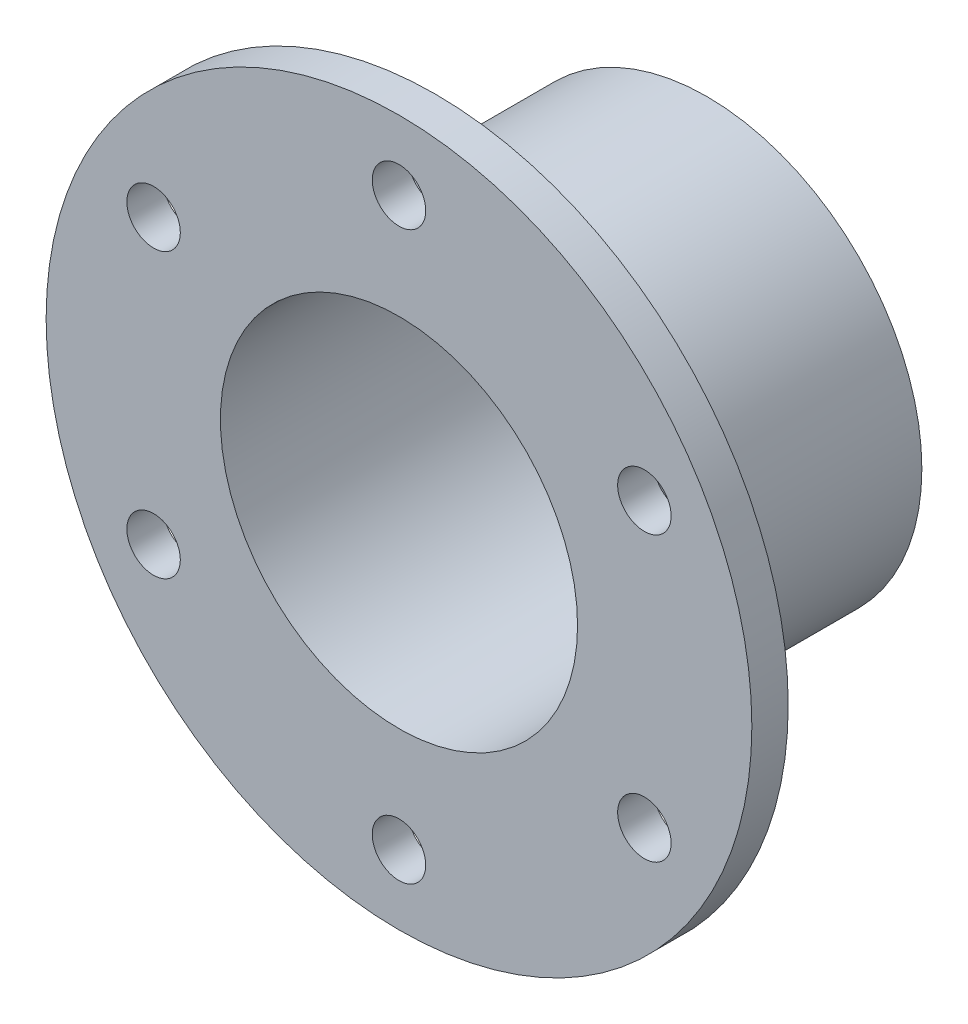
SolidWorks part; units mm, degrees
material "PVC Rígido"
ref_plane "Alzado" through (0, 0, 0) normal (0, 0, 1) x (1, 0, 0)
ref_plane "Planta" through (0, 0, 0) normal (0, 1, 0) x (1, 0, 0)
ref_plane "Vista lateral" through (0, 0, 0) normal (1, 0, 0) x (0, 0, -1)
sketch "Croquis1" plane through (0, 0, 0) normal (0, 0, 1) x (1, 0, 0)
  circle A0 centre (0, 0) radius 16.7
  circle A1 centre (0, 0) radius 20.1
  dimension "D1" = 33.4
  dimension "D2" = 40.2
extrude "Saliente-Extruir1" add sketch "Croquis1" along normal blind 25.4
sketch "Croquis2" plane through (0, 0, 25.4) normal (0, 0, 1) x (1, 0, 0)
  line L0 (0, 0) -> (0, 26.5) construction
  circle A0 centre (0, 0) radius 16.7
  circle A1 centre (0, 0) radius 33
  circle A3 centre (0, 26.5) radius 2.5
  circle A4 centre (22.9497, 13.25) radius 2.5
  circle A5 centre (22.9497, -13.25) radius 2.5
  circle A6 centre (0, -26.5) radius 2.5
  circle A7 centre (-22.9497, -13.25) radius 2.5
  circle A8 centre (-22.9497, 13.25) radius 2.5
  point P20 (0, 0)
  dimension "D1" = 33.4
  dimension "D2" = 66
  dimension "D3" = 26.5
  dimension "D4" = 5
  dimension "D6" = 26.5
  dimension "D5" = 6
extrude "Saliente-Extruir2" add sketch "Croquis2" along normal blind 3.4
